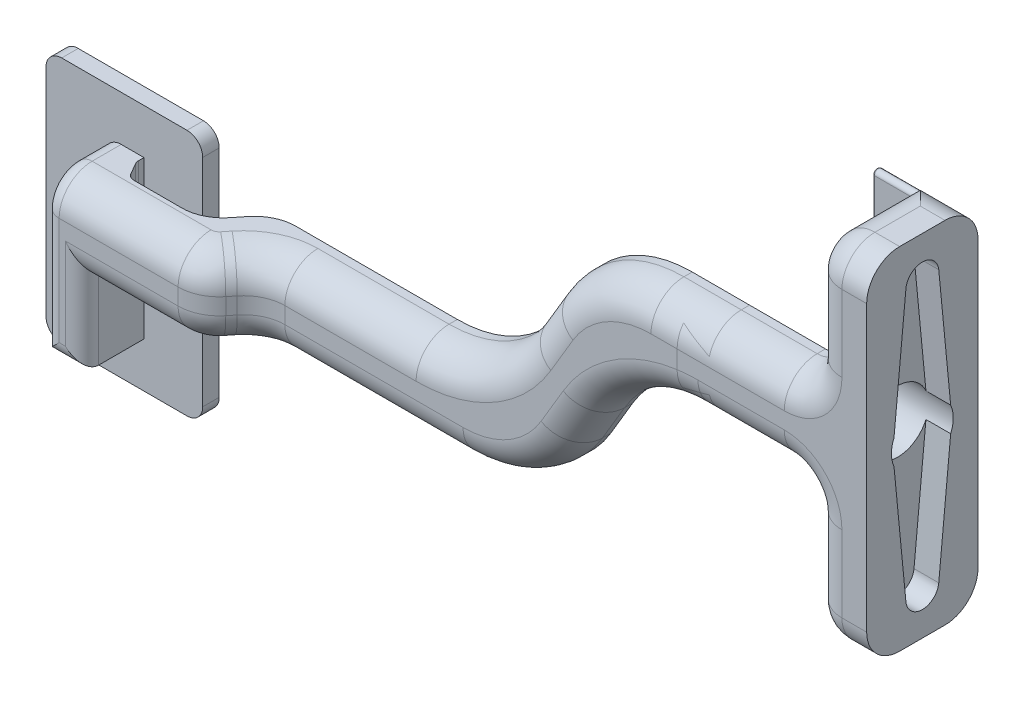
SolidWorks part; units mm, degrees
note: The reader was unsure of these and kept them because the rebuilt part matched: shared geometry of "Sketch13<3>".
ref_plane "Front Plane" through (0, 0, 0) normal (0, 0, 1) x (1, 0, 0)
ref_plane "Top Plane" through (0, 0, 0) normal (0, 1, 0) x (1, 0, 0)
ref_plane "Right Plane" through (0, 0, 0) normal (1, 0, 0) x (0, 0, -1)
sketch "Sketch1" plane through (0, 0, 0) normal (0, 0, 1) x (1, 0, 0)
  line L1 (-9.5, 15) -> (9.5, 15)
  line L2 (-9.5, 15) -> (-9.5, -15)
  line L3 (-9.5, -15) -> (9.5, -15)
  line L4 (9.5, 15) -> (9.5, -15)
  line L5 (-9.5, 15) -> (9.5, -15) construction
  line L6 (-9.5, -15) -> (9.5, 15) construction
  point P0 (0, 0)
  dimension "D1" = 19
  dimension "D2" = 30
extrude "Boss-Extrude1" add sketch "Sketch1" along normal blind 2
fillet "Fillet1" radius 1.905 4 edges at (9.5, -15, 1) (-9.5, -15, 1) (-9.5, 15, 1) (9.5, 15, 1)
sketch "Sketch2" plane through (0, 0, 2) normal (0, 0, 1) x (1, 0, 0)
  line L1 (-2.3813, 9.525) -> (2.3812, 9.525)
  line L2 (-2.3813, 9.525) -> (-2.3812, -9.525)
  line L3 (-2.3812, -9.525) -> (2.3813, -9.525)
  line L4 (2.3812, 9.525) -> (2.3813, -9.525)
  line L5 (-2.3813, 9.525) -> (2.3813, -9.525) construction
  line L6 (-2.3812, -9.525) -> (2.3812, 9.525) construction
  point P0 (0, 0)
  dimension "D1" = 19.05
  dimension "D2" = 4.7625
extrude "Boss-Extrude2" add sketch "Sketch2" along normal offset from surface (7.525 mm away) 9.525 up to face at (0, 0, 0)
sketch "Sketch9" plane through (0, 0, 9.525) normal (0, 0, 1) x (1, 0, 0)
  line L0 (-2.3813, 9.525) -> (46.922, 9.525)
  line L1 (46.922, 9.525) -> (58.3194, 28.75)
  line L2 (58.3194, 28.75) -> (86.0162, 28.75)
  line L3 (-2.3813, -0.475) -> (52.6187, -0.475)
  line L4 (52.6187, -0.475) -> (64.0162, 18.75)
  line L5 (64.0162, 18.75) -> (86.0162, 18.75)
  line L6 (-2.3813, 9.525) -> (-2.3813, -0.475)
  line L7 (86.0162, 28.75) -> (86.0162, 18.75)
  dimension "D2" = 29.225
  dimension "D3" = 55
  dimension "D4" = 22
  dimension "D5" = 88.3975
  dimension "D1" = 10
extrude "Boss-Extrude5" add sketch "Sketch9" against normal up to surface (9.525 mm away) up to face at (0, 0, 0)
sketch "Sketch10" plane through (0, -0.475, 0) normal (0, -1, 0) x (1, 0, 0)
  line L1 (86.0162, 0) -> (64.0162, 0) construction
  line L2 (2.3813, 5) -> (12.3813, 5)
  line L3 (2.3813, 9.525) -> (2.3813, 2) construction
  line L4 (12.3813, 5) -> (16.3813, 0)
  line L5 (9.5, 0) -> (52.6187, 0) construction
  line L6 (2.3813, 5) -> (2.3813, 2)
  line L7 (2.3813, 2) -> (9.5, 2)
  line L8 (9.5, 2) -> (9.5, 0)
  line L10 (9.5, 0) -> (16.3813, 0)
  line L12 (16.445, 9.525) -> (20.065, 5)
  line L13 (2.3813, 9.525) -> (52.6187, 9.525) construction
  line L14 (20.065, 5) -> (86.0162, 5)
  line L15 (86.0162, 0) -> (86.0162, 9.525) construction
  line L16 (86.0162, 5) -> (86.0162, 9.525)
  line L17 (86.0162, 9.525) -> (16.445, 9.525)
  dimension "D1" = 10
  dimension "D2" = 3
  dimension "D3" = 4
  dimension "D4" = 6
  dimension "D5" = 5
extrude "Cut-Extrude1" cut sketch "Sketch10" against normal through all
sketch "Sketch12" plane through (86.0162, 0, 0) normal (1, 0, 0) x (0, 0, -1)
  line L0 (0, 18.75) -> (-5, 18.75) construction
  line L1 (8.5, 45) -> (-5, 45)
  line L2 (8.5, 45) -> (8.5, 2.5)
  line L3 (8.5, 2.5) -> (-5, 2.5)
  line L4 (-5, 45) -> (-5, 2.5)
  line L5 (-5, 28.75) -> (-5, 18.75) construction
  dimension "D1" = 13.5
  dimension "D2" = 42.5
  dimension "D5" = 16.25
extrude "Boss-Extrude6" add sketch "Sketch12" along normal blind 7
sketch "Sketch13" plane through (93.0162, 0, 0) normal (1, 0, 0) x (0, 0, -1)
  line L0 (-5, 45) -> (-5, 2.5) construction
  line L1 (8.5, 45) -> (-5, 45) construction
  line L2 (1.75, 7.5) -> (1.75, 23.75) construction
  line L3 (1.75, 23.75) -> (1.75, 40) construction
  line L4 (-0.2407, 7.3073) -> (-1.6869, 22.25)
  line L5 (1.75, 23.75) -> (-11.3877, 23.75) construction
  line L6 (3.7407, 7.3073) -> (5.1869, 22.25)
  line L7 (-0.2407, 40.1927) -> (-1.6869, 25.25)
  line L8 (3.7407, 40.1927) -> (5.1869, 25.25)
  circle A0 centre (1.75, 23.75) radius 3.75
  circle A1 centre (1.75, 7.5) radius 2
  circle A2 centre (1.75, 40) radius 2
  point P0 (1.75, 23.75)
  point P3 (-5, 23.75)
  point P7 (1.75, 45)
  point P13 (1.75, 42)
  point P14 (1.75, 5.5)
  dimension "D1" = 7.5
  dimension "D2" = 4
  dimension "D3" = 36.5
  dimension "D4" = 3
extrude "Cut-Extrude2" cut sketch "Sketch13" against normal blind 3 contours A2 | A2 L7 A0 L8 | A0 | A1 L6 A0 L4 | A1
extrude "Cut-Extrude3" cut sketch "Sketch13<3>" against normal blind 17 contours A0
sketch "Sketch13<3>" plane through (93.0162, 0, 0) normal (1, 0, 0) x (0, 0, -1) same geometry as "Sketch13"
fillet "Fillet2" radius 4 4 edges at (89.5162, 2.5, -8.5) (89.5162, 2.5, 5) (89.5162, 45, 5) (89.5162, 45, -8.5)
fillet "Fillet3" radius 15 4 edges at (46.922, 9.525, 2.5) (52.6187, -0.475, 2.5) (64.0162, 18.75, 2.5) (58.3194, 28.75, 2.5)
fillet "Fillet4" radius 3 2 edges at (86.0162, 28.75, 2.5) (86.0162, 18.75, 2.5)
fillet "Fillet5" radius 5 4 edges at (12.3813, 4.525, 5) (16.3813, 4.525, 0) (16.445, 4.525, 9.525) (20.065, 4.525, 5)
chamfer "Chamfer1" distance 1.2 angle 60 1 edges at (2.3813, 4.525, 5)
fillet "Fillet8" radius 1 2 edges at (3.5813, 4.525, 5) (2.3813, 4.525, 2.9215)
fillet "Fillet9" radius 1 1 edges at (76.0162, 23.75, 2)
sketch "Sketch16" [suppressed] plane through (86.025, 0, 0) normal (-1, 0, 0) x (0, 0, 1)
  line L9 (-1, 28.4404) -> (-1, 32.75)
  line L10 (-1, 28.4404) -> (-1, 32.75)
  line L11 (-1, 32.75) -> (4, 32.75)
  line L12 (-1, 32.75) -> (4, 32.75)
  line L13 (4, 14.75) -> (-1, 14.75)
  line L14 (4, 14.75) -> (-1, 14.75)
  line L15 (-1, 14.75) -> (-1, 19.0596)
  line L16 (-1, 14.75) -> (-1, 19.0596)
  line L17 (4, 32.75) -> (4, 41)
  line L18 (4, 32.75) -> (4, 41)
  line L19 (1, 44) -> (-4.5, 44)
  line L20 (1, 44) -> (-4.5, 44)
  line L21 (-7.5, 41) -> (-7.5, 6.5)
  line L22 (-7.5, 41) -> (-7.5, 6.5)
  line L28 (-1.75, 23.75) -> (7.9034, 23.75) construction
  line L29 (0, 34.0651) -> (5, 34.0651)
  line L30 (-1, 19.0596) -> (-1, 33.0651)
  line L31 (-1, 32.75) -> (-1, 28.4404)
  line L32 (4, 32.75) -> (-1, 32.75)
  line L33 (4, 41) -> (4, 32.75)
  line L34 (-4.5, 3.5) -> (1, 3.5)
  line L35 (-4.5, 3.5) -> (1, 3.5)
  line L36 (4, 6.5) -> (4, 14.75)
  line L37 (4, 6.5) -> (4, 14.75)
  arc A5 (4, 41) -> (1, 44) centre (1, 41) ccw
  arc A6 (4, 41) -> (1, 44) centre (1, 41) ccw
  arc A7 (-4.5, 44) -> (-7.5, 41) centre (-4.5, 41) ccw
  arc A8 (-4.5, 44) -> (-7.5, 41) centre (-4.5, 41) ccw
  arc A9 (-7.5, 6.5) -> (-4.5, 3.5) centre (-4.5, 6.5) ccw
  arc A10 (-7.5, 6.5) -> (-4.5, 3.5) centre (-4.5, 6.5) ccw
  arc A11 (-1, 28.4404) -> (-1, 19.0596) centre (-1.75, 23.75) ccw
  arc A12 (1, 3.5) -> (4, 6.5) centre (1, 6.5) ccw
  arc A14 (-1, 28.4404) -> (-1, 19.0596) centre (-1.75, 23.75) ccw
  arc A16 (-1, 33.0651) -> (0, 34.0651) centre (0, 33.0651) cw
  arc A17 (-1, 19.0596) -> (-1, 28.4404) centre (-1.75, 23.75) cw
  arc A18 (5, 34.0651) -> (4, 41) centre (4.5, 37.5325) cw
  arc A19 (1, 3.5) -> (4, 6.5) centre (1, 6.5) ccw
  dimension "D1" = 1
sketch "Sketch17" plane through (86.0162, 0, 0) normal (-1, 0, 0) x (0, 0, 1)
  line L0 (-6.75, 44.3072) -> (-6.75, 3.1928)
  line L1 (0, 20.4334) -> (0, 15.75) construction
  line L9 (0, 27.0666) -> (0, 31.75)
  line L10 (0, 31.75) -> (5, 31.75)
  line L11 (5, 31.75) -> (5, 41)
  line L12 (1, 45) -> (-4.5, 45)
  line L13 (-8.5, 41) -> (-8.5, 6.5)
  line L14 (-4.5, 2.5) -> (1, 2.5)
  line L15 (5, 6.5) -> (5, 15.75)
  line L16 (5, 15.75) -> (0, 15.75)
  line L17 (0, 15.75) -> (0, 20.4334)
  line L22 (-8.5, 41) -> (-8.5, 6.5)
  arc A5 (5, 41) -> (1, 45) centre (1, 41) ccw
  arc A6 (-4.5, 45) -> (-8.5, 41) centre (-4.5, 41) ccw
  arc A7 (-8.5, 6.5) -> (-4.5, 2.5) centre (-4.5, 6.5) ccw
  arc A8 (1, 2.5) -> (5, 6.5) centre (1, 6.5) ccw
  arc A9 (0, 27.0666) -> (0, 20.4334) centre (-1.75, 23.75) ccw
  arc A11 (-6.75, 44.3072) -> (-8.5, 41) centre (-4.5, 41) ccw
  arc A12 (-8.5, 6.5) -> (-6.75, 3.1928) centre (-4.5, 6.5) ccw
  dimension "D2" = 6.75
  dimension "D1" = 0
extrude "Boss-Extrude7" add sketch "Sketch17" along normal blind 4
fillet "Fillet10" radius 4 26 edges at (20.3022, -0.475, 5.4935) (18.255, -0.475, 7.2625) (16.2078, -0.475, 9.0315) (8.2116, -0.475, 9.525) (86.0162, 45, -1.75) (86.0162, 2.5, -1.75) (86.0162, 36.375, 5) (86.0162, 11.125, 5) (85.1375, 17.8713, 5) (77.7888, 18.75, 5) (65.1365, 16.7835, 5) (58.3175, 9.1375, 5) (33.2708, -0.475, 5) (51.4984, 1.4915, 5) (5.8303, 9.525, 9.525) (18.255, 9.525, 7.2625) (16.2078, 9.525, 9.0315) (20.3022, 9.525, 5.4935) (30.4224, 9.525, 5) (45.8017, 11.4915, 5) (52.6207, 19.1375, 5) (59.4397, 26.7835, 5) (85.1375, 29.6287, 5) (74.9404, 28.75, 5) (86.0162, 43.8284, 3.8284) (86.0162, 3.6716, 3.8284)
fillet "Fillet11" radius 2 5 edges at (-2.3813, 9.525, 3.7625) (-2.3813, 8.3534, 8.3534) (-2.3812, -2, 9.525) (0, -9.525, 9.525) (2.3813, -3, 9.525)
fillet "Fillet12" radius 0.5 2 edges at (84.8912, 3.1928, -6.75) (84.8912, 44.3072, -6.75)
fillet "Fillet13" radius 0.2 6 edges at (82.0162, 23.75, -8.5) (82.0162, 42.3093, -8.2796) (82.0162, 43.6375, -7.0863) (82.0162, 3.8625, -7.0863) (82.0162, 5.1907, -8.2796) (82.0162, 23.75, -6.75)
sketch "Sketch19" plane through (0, 0, 5) normal (0, 0, 1) x (1, 0, 0)
  line L0 (73.8114, 28.75) -> (73.8114, 25.75)
  line L1 (66.8646, 28.75) -> (83.0162, 28.75) construction
  line L2 (73.8114, 25.75) -> (70.0336, 27.125)
  line L3 (70.0336, 27.125) -> (70.0336, 20.375)
  line L4 (93.0162, 23.75) -> (51.9037, 23.75) construction
  line L5 (93.0162, 41) -> (93.0162, 6.5) construction
  line L6 (73.8114, 21.75) -> (70.0336, 20.375)
  line L7 (73.8114, 18.75) -> (73.8114, 21.75)
  line L8 (72.5614, 22.75) -> (72.5614, 18.75) construction
  point P12 (70.0336, 23.75)
  dimension "D1" = 1.25
  dimension "D2" = 3
  dimension "D3" = 70
  dimension "D4" = 6.75
surface "Surface-Extrude1" sketch "Sketch19" parameters "D1"=32
split "Split1" trimming surface bodies 117 bodies to split 116 resulting bodies 118 119
other "Save Bodies1"
